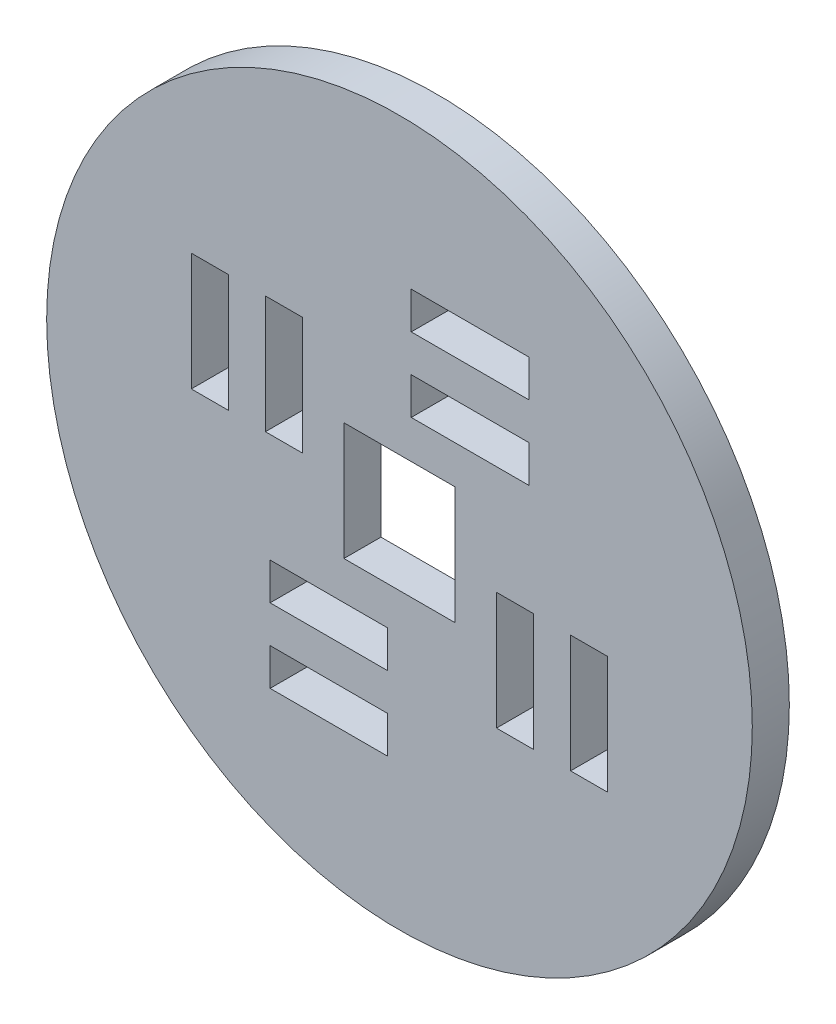
SolidWorks part; units mm, degrees
material "Hexcel AS4C (3000 Filaments)"
ref_plane "Front Plane" through (0, 0, 0) normal (0, 0, 1) x (1, 0, 0)
ref_plane "Top Plane" through (0, 0, 0) normal (0, 1, 0) x (1, 0, 0)
ref_plane "Right Plane" through (0, 0, 0) normal (1, 0, 0) x (0, 0, -1)
sketch "Sketch1" plane through (0, 0, 0) normal (0, 0, 1) x (1, 0, 0)
  circle A0 centre (0, 0) radius 38.1
  dimension "D1" = 76.2
extrude "Boss-Extrude1" add sketch "Sketch1" along normal blind 4 contours A0
sketch "Sketch2" plane through (0, 0, 4) normal (0, 0, 1) x (1, 0, 0)
  line L0 (-1.27, -10.478) -> (-13.97, -10.478)
  line L1 (10.478, -1.27) -> (14.478, -1.27)
  line L2 (10.478, -1.27) -> (10.478, -13.97)
  line L3 (10.478, -13.97) -> (14.478, -13.97)
  line L4 (14.478, -1.27) -> (14.478, -13.97)
  line L5 (18.478, -1.27) -> (22.478, -1.27)
  line L6 (18.478, -1.27) -> (18.478, -13.97)
  line L7 (18.478, -13.97) -> (22.478, -13.97)
  line L8 (22.478, -1.27) -> (22.478, -13.97)
  line L9 (-1.27, -10.478) -> (-1.27, -14.478)
  line L10 (-1.27, -14.478) -> (-13.97, -14.478)
  line L11 (-13.97, -10.478) -> (-13.97, -14.478)
  line L12 (-1.27, -18.478) -> (-13.97, -18.478)
  line L13 (-1.27, -18.478) -> (-1.27, -22.478)
  line L14 (-1.27, -22.478) -> (-13.97, -22.478)
  line L15 (-13.97, -18.478) -> (-13.97, -22.478)
  line L16 (-10.478, 1.27) -> (-10.478, 13.97)
  line L17 (-10.478, 1.27) -> (-14.478, 1.27)
  line L18 (-14.478, 1.27) -> (-14.478, 13.97)
  line L19 (-10.478, 13.97) -> (-14.478, 13.97)
  line L20 (-18.478, 1.27) -> (-18.478, 13.97)
  line L21 (-18.478, 1.27) -> (-22.478, 1.27)
  line L22 (-22.478, 1.27) -> (-22.478, 13.97)
  line L23 (-18.478, 13.97) -> (-22.478, 13.97)
  line L24 (1.27, 10.478) -> (13.97, 10.478)
  line L25 (1.27, 10.478) -> (1.27, 14.478)
  line L26 (1.27, 14.478) -> (13.97, 14.478)
  line L27 (13.97, 10.478) -> (13.97, 14.478)
  line L28 (1.27, 18.478) -> (13.97, 18.478)
  line L29 (1.27, 18.478) -> (1.27, 22.478)
  line L30 (1.27, 22.478) -> (13.97, 22.478)
  line L31 (13.97, 18.478) -> (13.97, 22.478)
  point P37 (0, 0)
  dimension "D1" = 4
  dimension "D2" = 4
  dimension "D3" = 4
  dimension "D4" = 12.7
  dimension "D5" = 14.478
  dimension "D6" = 1.27
  dimension "D7" = 4
extrude "Cut-Extrude1" cut sketch "Sketch2" against normal through all
sketch "Sketch3" plane through (0, 0, 4) normal (0, 0, 1) x (1, 0, 0)
  line L1 (-6, -6.35) -> (6, -6.35)
  line L2 (-6, -6.35) -> (-6, 6.35)
  line L3 (-6, 6.35) -> (6, 6.35)
  line L4 (6, -6.35) -> (6, 6.35)
  line L5 (-6, -6.35) -> (6, 6.35) construction
  line L6 (-6, 6.35) -> (6, -6.35) construction
  point P0 (0, 0)
  dimension "D1" = 12
  dimension "D2" = 12.7
extrude "Cut-Extrude2" cut sketch "Sketch3" against normal up to next
